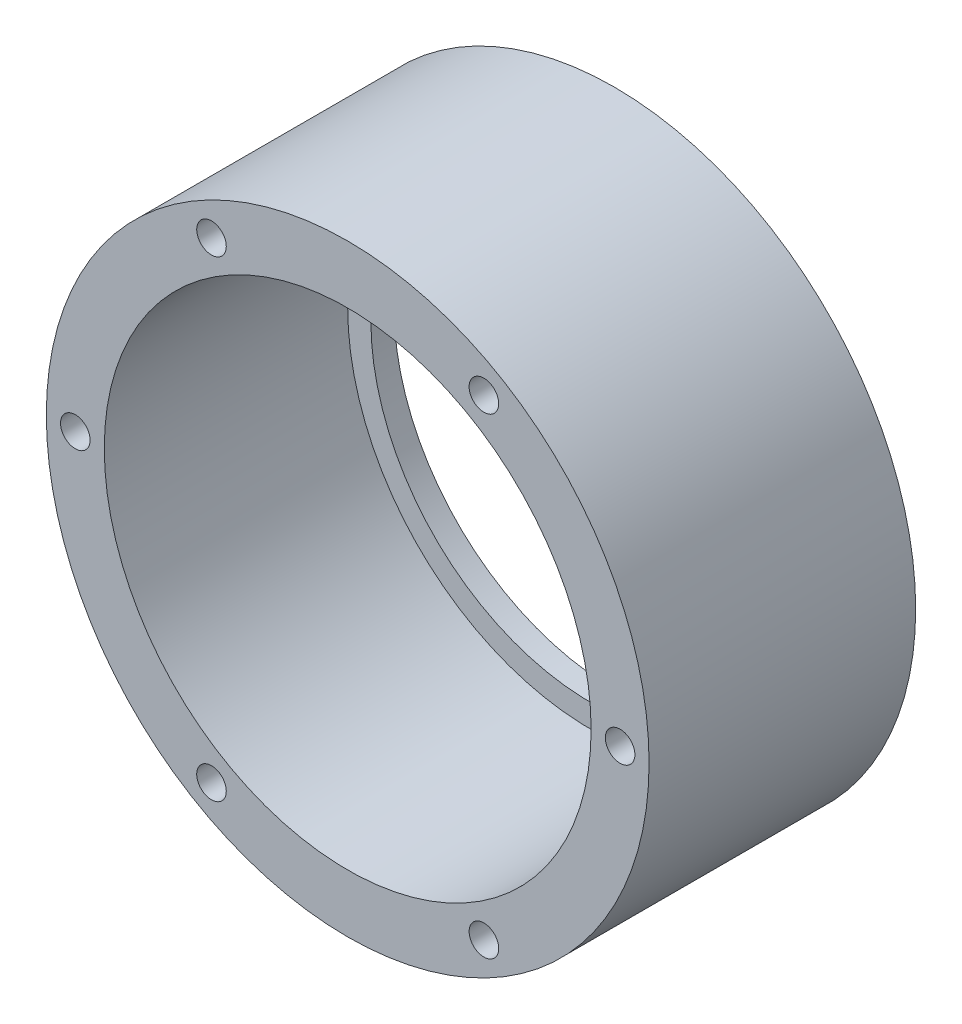
SolidWorks part; units mm, degrees
material "1060 Сплав"
ref_plane "Спереди" through (0, 0, 0) normal (0, 0, 1) x (1, 0, 0)
ref_plane "Сверху" through (0, 0, 0) normal (0, 1, 0) x (1, 0, 0)
ref_plane "Справа" through (0, 0, 0) normal (1, 0, 0) x (0, 0, -1)
sketch "Эскиз1" plane through (0, 0, 0) normal (1, 0, 0) x (0, 0, -1)
  line L3 (0, 26) -> (23, 26)
  line L4 (23, 26) -> (23, 19)
  line L6 (23, 19) -> (21, 19)
  line L7 (21, 19) -> (21, 21)
  line L8 (21, 21) -> (0, 21)
  line L9 (0, 0) -> (56.4457, 0) construction
  line L10 (0, 21) -> (0, 26)
  point P1 (0, 0)
  dimension "D1" = 42
  dimension "D2" = 38
  dimension "D3" = 52
  dimension "D4" = 2
  dimension "D5" = 23
revolve "Повернуть1" add sketch "Эскиз1" angle 360 about L9
hole_wizard "Сверло под метчик  спиральное M2.51" positions "Эскиз2" profile "Эскиз3" hole size "M2.5x0.45" standard "DIN"
sketch "Эскиз2" plane through (0, 0, 0) normal (0, 0, 1) x (1, 0, 0)
  point P0 (23.5, 0)
  dimension "D1" = 23.5
sketch "Эскиз3" plane through (23.5, 0, 0) normal (1, 0, 0) x (0, -1, 0)
  line L0 (0, 0) -> (0, 8.7661)
  line L1 (0, 8.7661) -> (1.275, 8)
  line L2 (1.275, 8) -> (1.275, 0)
  line L5 (1.275, 0) -> (0, 0)
  line L10 (0, 8.7661) -> (-1.275, 8) construction
  line L11 (0, -6.35) -> (0, 107.95) construction
  dimension "Диаметр отверстия" = 2.55
  dimension "Глубина отверстия" = 8
  dimension "Угол заточки сверла" = 118
pattern_circular "Круговой массив1" count 6 over 360 about axis through (0, 0, 0) along (0, 0, 1) of "Сверло под метчик  спиральное M2.51"
